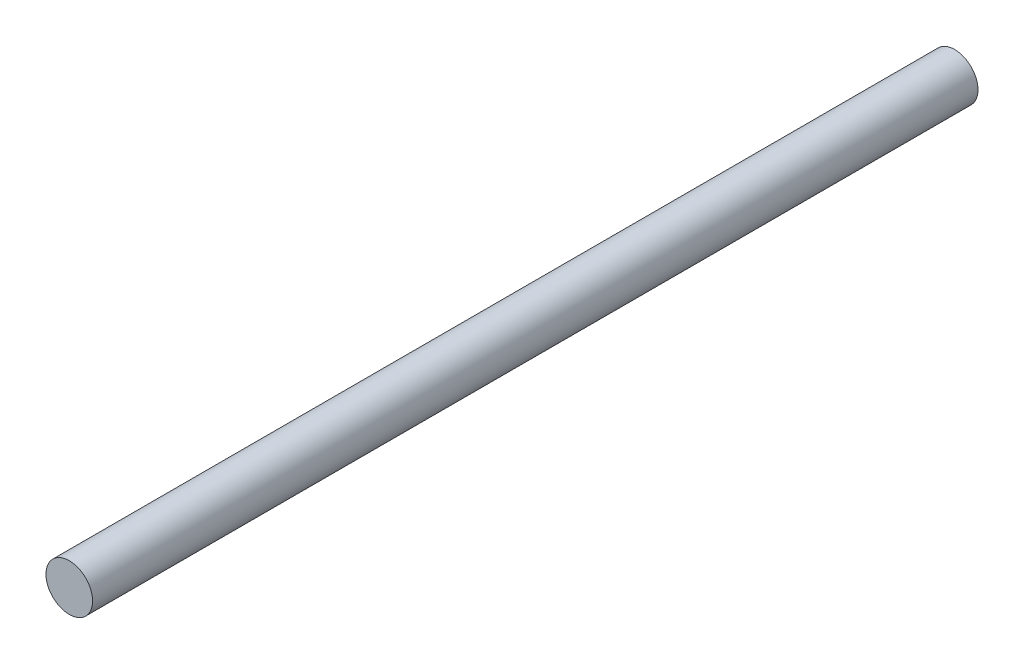
SolidWorks part; units mm, degrees
ref_plane "前基準面" through (0, 0, 0) normal (0, 0, 1) x (1, 0, 0)
ref_plane "上基準面" through (0, 0, 0) normal (0, 1, 0) x (1, 0, 0)
ref_plane "右基準面" through (0, 0, 0) normal (1, 0, 0) x (0, 0, -1)
ref_axis "基準軸1" through (0, -55, 0) along (0, 1, 0)
ref_axis "基準軸2" through (-88.99, 0, 0) along (1, 0, 0)
ref_axis "基準軸3" through (0, 0, 55) along (0, 0, -1)
sketch "草圖1" plane through (0, 0, 0) normal (0, 0, 1) x (1, 0, 0)
  circle A0 centre (0, 0) radius 2.5
  dimension "D1" = 5
extrude "填料-伸長1" add sketch "草圖1" along normal blind 95
